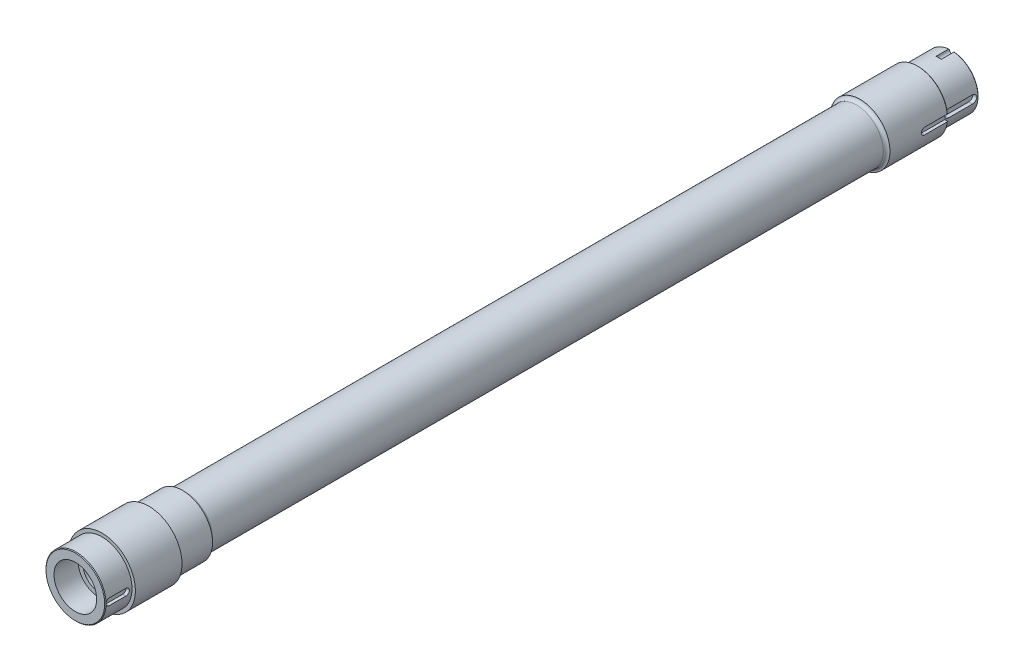
SolidWorks part; units mm, degrees
ref_plane "前视基准面" through (0, 0, 0) normal (0, 0, 1) x (1, 0, 0)
ref_plane "上视基准面" through (0, 0, 0) normal (0, 1, 0) x (1, 0, 0)
ref_plane "右视基准面" through (0, 0, 0) normal (1, 0, 0) x (0, 0, -1)
other "Configuration Table"
sketch "草图1" plane through (0, 0, 0) normal (1, 0, 0) x (0, 0, -1)
  line L0 (0, 0) -> (-55.6485, 0) construction
  line L1 (0, 0) -> (0, 22.5)
  line L2 (0, 22.5) -> (20, 22.5)
  line L3 (20, 22.5) -> (20, 25)
  line L4 (20, 25) -> (55, 25)
  line L5 (55, 25) -> (55, 22.5)
  line L6 (55, 22.5) -> (80.4, 22.5)
  line L7 (82.9, 20) -> (585.8, 20)
  line L8 (588.3, 22.5) -> (631.9, 22.5)
  line L9 (631.9, 22.5) -> (631.9, 20)
  line L10 (631.9, 20) -> (657.3, 20)
  line L11 (657.3, 20) -> (657.3, 0)
  line L12 (657.3, 0) -> (0, 0)
  arc A0 (80.4, 22.5) -> (82.9, 20) centre (82.9, 22.5) ccw
  arc A1 (585.8, 20) -> (588.3, 22.5) centre (585.8, 22.5) ccw
  dimension "D3" = 2.5
  dimension "D1" = 45
  dimension "D2" = 50
  dimension "D4" = 35
  dimension "D5" = 25.4
  dimension "D6" = 20
  dimension "D7" = 507.9
  dimension "D8" = 611.9
  dimension "D9" = 25.4
  dimension "D10" = 20
  dimension "D11" = 20
revolve "旋转1" add sketch "草图1" angle 360 about L0
sketch "草图2" plane through (0, 0, 0) normal (1, 0, 0) x (0, 0, -1)
  line L0 (0, 0) -> (654.1215, 0) construction
  line L1 (631.9, 0) -> (657.3, 0) construction
  line L2 (588.3, 0) -> (631.9, 0) construction
  line L3 (0, 0) -> (0, 16)
  line L4 (0, 22.5) -> (0, -22.5) construction
  line L5 (0, 16) -> (18, 16)
  line L6 (18, 16) -> (18, 12.5)
  line L7 (18, 12.5) -> (643.3, 12.5)
  line L8 (643.3, 12.5) -> (643.3, 14)
  line L9 (643.3, 14) -> (657.3, 14)
  line L10 (657.3, -20) -> (657.3, 20) construction
  line L11 (657.3, 14) -> (657.3, 0)
  line L12 (657.3, 0) -> (0, 0)
  dimension "D1" = 14
  dimension "D2" = 12.5
  dimension "D3" = 14
  dimension "D4" = 16
  dimension "D5" = 18
revolve "切除-旋转1" cut sketch "草图2" angle 360 about L0
ref_plane "基准面1" through (20, 0, 0) normal (1, 0, 0) x (0, 0, -1)
chamfer "倒角1" distance 0.5 angle 45 4 edges at (14, 0, -657.3) (-20, 0, -657.3) (-22.5, 0, -631.9) (-22.5, 0, 0)
sketch "草图3" plane through (20, 0, 0) normal (1, 0, 0) x (0, 0, -1)
  line L0 (3, 0) -> (15.5, 0) construction
  line L1 (3, 2.5) -> (15.5, 2.5)
  line L2 (3, -2.5) -> (15.5, -2.5)
  line L4 (0.5, -22.5) -> (0.5, 22.5) construction
  arc A0 (3, 2.5) -> (3, -2.5) centre (3, 0) ccw
  arc A1 (15.5, -2.5) -> (15.5, 2.5) centre (15.5, 0) ccw
  point P2 (9.25, 0)
  dimension "D1" = 5
  dimension "D2" = 18
extrude "切除-拉伸3" cut sketch "草图3" along normal blind 10
sketch "草图4" plane through (20, 0, 0) normal (1, 0, 0) x (0, 0, -1)
  line L0 (631.9, 2.5) -> (614.4, 2.5)
  line L1 (631.9, -22) -> (631.9, 22) construction
  line L2 (614.4, -2.5) -> (631.9, -2.5)
  line L3 (631.9, -2.5) -> (631.9, 2.5)
  line L6 (588.3, 22.5) -> (588.3, -22.5) construction
  arc A0 (614.4, 2.5) -> (614.4, -2.5) centre (614.4, 0) ccw
  point P6 (631.9, 0)
  dimension "D2" = 23.6
  dimension "D1" = 5
extrude "切除-拉伸4" cut sketch "草图4" along normal blind 10
ref_plane "基准面2" through (17, 0, 0) normal (1, 0, 0) x (0, 0, -1)
sketch "草图5" plane through (17, 0, 0) normal (1, 0, 0) x (0, 0, -1)
  line L0 (634.9, 0) -> (652.9, 0) construction
  line L1 (634.9, 3) -> (652.9, 3)
  line L2 (634.9, -3) -> (652.9, -3)
  line L3 (631.9, -20) -> (631.9, 20) construction
  arc A0 (634.9, 3) -> (634.9, -3) centre (634.9, 0) ccw
  arc A1 (652.9, -3) -> (652.9, 3) centre (652.9, 0) ccw
  point P2 (643.9, 0)
  dimension "D1" = 6
  dimension "D2" = 18
extrude "切除-拉伸5" cut sketch "草图5" along normal blind 10
mirror "镜向1" about plane through (0, 0, 0) normal (1, 0, 0) of "切除-拉伸5", "切除-拉伸3"
sketch "草图6" plane through (0, 0, -657.3) normal (0, 0, 1) x (1, 0, 0)
  line L0 (0, 0) -> (-20, 0) construction
  circle A0 centre (0, 0) radius 19.5 construction
  circle A1 centre (0, 19.5) radius 2
  arc A2 (20, 0) -> (-20, 0) centre (0, 0) ccw construction
  circle A3 centre (0, -19.5) radius 2
  dimension "D1" = 39
  dimension "D2" = 4
extrude "切除-拉伸7" cut sketch "草图6" along normal blind 10
